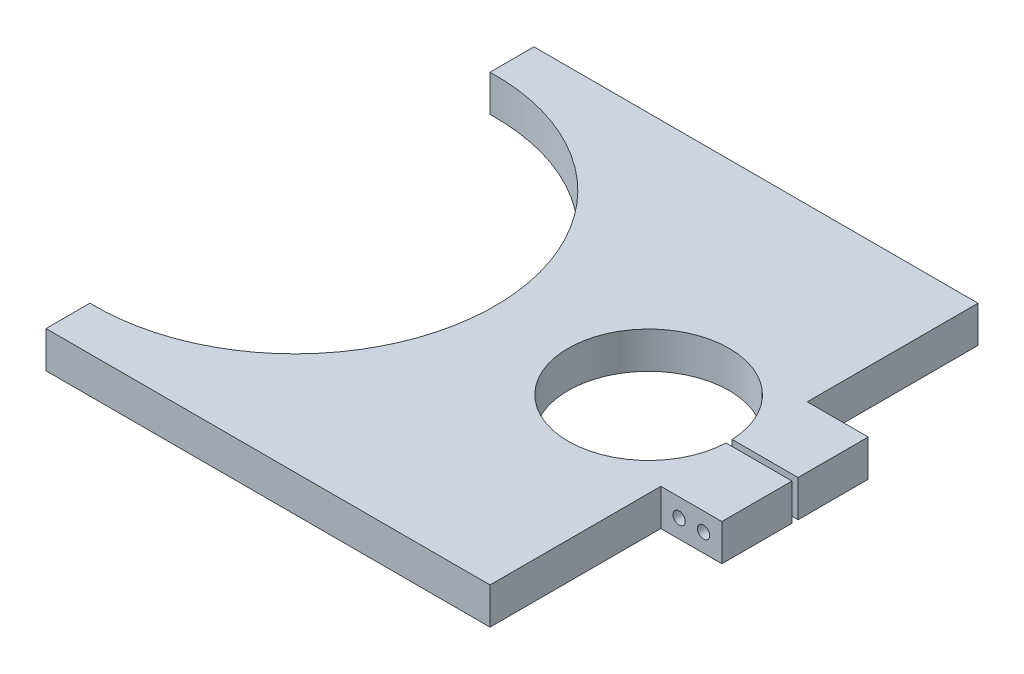
SolidWorks part; units mm, degrees
ref_plane "Front Plane" through (0, 0, 0) normal (0, 0, 1) x (1, 0, 0)
ref_plane "Top Plane" through (0, 0, 0) normal (0, 1, 0) x (1, 0, 0)
ref_plane "Right Plane" through (0, 0, 0) normal (1, 0, 0) x (0, 0, -1)
sketch "Sketch1" plane through (0, 0, 0) normal (0, 1, 0) x (1, 0, 0)
  line L0 (53.34, 127) -> (53.34, 0) construction
  line L1 (0, 0) -> (131.445, 0)
  line L2 (0, 0) -> (0, 11.43)
  line L3 (0, 127) -> (131.445, 127)
  line L5 (0, 115.57) -> (0, 127)
  line L6 (131.445, 0) -> (131.445, 127)
  line L7 (72.39, 63.5) -> (72.39, 0) construction
  arc A0 (0, 115.57) -> (0, 11.43) centre (1.2549, 63.5) cw
  circle A1 centre (93.345, 63.5) radius 20.955
  point P7 (0, 115.57)
  point P8 (0, 11.43)
  dimension "D1" = 127
  dimension "D2" = 19.05
  dimension "D3" = 53.34
  dimension "D4" = 11.43
  dimension "D5" = 11.43
  dimension "D7" = 38.1
extrude "Boss-Extrude1" add sketch "Sketch1" along normal blind 9.525
sketch "Sketch3" plane through (0, 9.525, 0) normal (0, 1, 0) x (1, 0, 0)
  line L0 (131.445, 0) -> (131.445, 127) construction
  line L1 (131.445, 64.2938) -> (111.7237, 64.2938)
  line L2 (131.445, 64.2938) -> (131.445, 62.7063)
  line L3 (131.445, 62.7063) -> (111.7237, 62.7063)
  line L4 (111.7237, 64.2938) -> (111.7237, 62.7063)
  line L5 (0, 0) -> (131.445, 0) construction
  dimension "D1" = 1.5875
  dimension "D2" = 62.7062
extrude "Cut-Extrude1" cut sketch "Sketch3" against normal through all
sketch "Sketch4" plane through (0, 9.525, 0) normal (0, 1, 0) x (1, 0, 0)
  line L1 (131.445, 127) -> (115.57, 127)
  line L2 (131.445, 127) -> (131.445, 82.55)
  line L3 (131.445, 82.55) -> (115.57, 82.55)
  line L4 (115.57, 127) -> (115.57, 82.55)
  line L5 (131.445, 127) -> (0, 127) construction
  line L6 (38.4112, 127) -> (115.57, 127)
  line L8 (131.445, 0) -> (115.57, 0)
  line L9 (131.445, 0) -> (131.445, 44.45)
  line L10 (131.445, 44.45) -> (115.57, 44.45)
  line L11 (115.57, 0) -> (115.57, 44.45)
  line M3 (131.445, 0) -> (131.445, 62.7063)
  line M7 (131.445, 64.2938) -> (131.445, 127)
  line M8 (131.445, 127) -> (0, 127)
  line M12 (0, 0) -> (131.445, 0)
  dimension "D2" = 15.875
  dimension "D3" = 44.45
  dimension "D4" = 15.875
extrude "Cut-Extrude5" cut sketch "Sketch4" against normal through all contours L11 L10 M12 M3 | L4 L3 M8 M7 region at (123.5075, 9.525, -104.775) region at (123.5075, 9.525, -22.225)
sketch "Sketch7" plane through (0, 0, -44.45) normal (0, 0, 1) x (1, 0, 0)
  line L0 (131.445, 0) -> (115.57, 0) construction
  line L1 (131.445, 0) -> (131.445, 9.525) construction
  circle A0 centre (126.6825, 4.7625) radius 1.5875
  circle A1 centre (120.3325, 4.7625) radius 1.5875
  dimension "D1" = 4.7625
  dimension "D2" = 4.7625
  dimension "D3" = 4.7625
  dimension "D4" = 6.35
extrude "Cut-Extrude6" cut sketch "Sketch7" against normal through all
